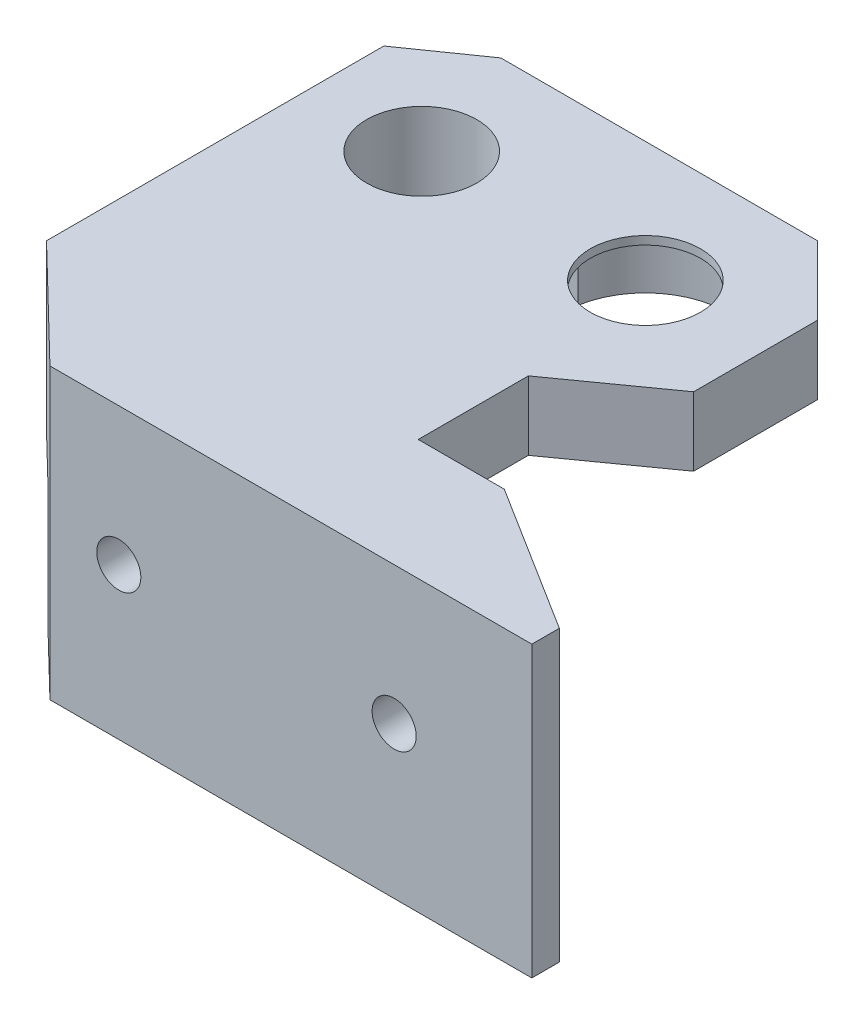
SolidWorks part; units mm, degrees
ref_plane "Front Plane" through (0, 0, 0) normal (0, 0, 1) x (1, 0, 0)
ref_plane "Top Plane" through (0, 0, 0) normal (0, 1, 0) x (1, 0, 0)
ref_plane "Right Plane" through (0, 0, 0) normal (1, 0, 0) x (0, 0, -1)
sketch "Sketch1" plane through (0, 0, 0) normal (0, 1, 0) x (1, 0, 0)
  line L0 (0, 0) -> (16.25, 0) construction
  line L5 (-3.75, 8.75) -> (19.25, 8.75)
  line L6 (19.25, 8.75) -> (24.25, 5.25)
  line L7 (24.25, 5.25) -> (24.25, -19.25)
  line L8 (24.25, -19.25) -> (16.25, -27)
  line L9 (16.25, -27) -> (-18.75, -27)
  line L10 (-18.75, -27) -> (-18.75, -25)
  line L11 (-18.75, -25) -> (-8, -18.25)
  line L12 (-8, -18.25) -> (-1.75, -18.25)
  line L13 (-1.75, -18.25) -> (-1.75, -10.25)
  line L14 (-1.75, -10.25) -> (-8.75, -5.25)
  line L15 (-8.75, -5.25) -> (-8.75, 3.75)
  line L16 (-8.75, 3.75) -> (-3.75, 8.75)
  line L17 (16.25, 0) -> (24.25, 0) construction
  circle A0 centre (0, 0) radius 4
  circle A1 centre (16.25, 0) radius 4
  point P0 (0, 0)
  dimension "D2" = 8
  dimension "D3" = 8
  dimension "D1" = 16.25
  dimension "D4" = 23
  dimension "D5" = 5
  dimension "D6" = 3.5
  dimension "D7" = 24.5
  dimension "D8" = 8
  dimension "D9" = 8.75
  dimension "D10" = 5
  dimension "D11" = 5
  dimension "D12" = 7
  dimension "D13" = 5
  dimension "D14" = 9
  dimension "D15" = 8
  dimension "D16" = 7.75
  dimension "D17" = 35
  dimension "D18" = 6.25
  dimension "D19" = 6.75
  dimension "D20" = 2
extrude "Boss-Extrude1" add sketch "Sketch1" along normal blind 5
sketch "Sketch2" plane through (0, 0, 0) normal (0, -1, 0) x (1, 0, 0)
  line L0 (24.25, 19.25) -> (24.25, -5.25)
  line L1 (24.25, -5.25) -> (20.75, -5.25)
  line L2 (20.75, -5.25) -> (20.75, 18.25)
  line L3 (20.75, 18.25) -> (-8, 18.25)
  line L4 (-8, 18.25) -> (-14.3704, 22.25)
  line L5 (-8, 18.25) -> (-18.75, 25) construction
  line L6 (-14.3704, 22.25) -> (21.1532, 22.25)
  line L7 (16.25, 27) -> (24.25, 19.25) construction
  line L8 (21.1532, 22.25) -> (24.25, 19.25)
  dimension "D1" = 3.5
  dimension "D2" = 4
extrude "Boss-Extrude2" add sketch "Sketch2" along normal blind 7
sketch "Sketch3" plane through (0, 0, 0) normal (0, -1, 0) x (1, 0, 0)
  line L5 (-14.3704, 22.25) -> (21.1532, 22.25)
  line L6 (21.1532, 22.25) -> (16.25, 27)
  line L7 (16.25, 27) -> (-18.75, 27)
  line L8 (-18.75, 27) -> (-18.75, 25)
  line L9 (-18.75, 25) -> (-14.3704, 22.25)
  line L10 (-14.3704, 22.25) -> (21.1532, 22.25)
  line L11 (21.1532, 22.25) -> (16.25, 27)
  line L12 (16.25, 27) -> (-18.75, 27)
  line L13 (-18.75, 27) -> (-18.75, 25)
  line L14 (-18.75, 25) -> (-14.3704, 22.25)
  dimension "D1" = 0
extrude "Boss-Extrude3" add sketch "Sketch3" along normal blind 16
sketch "Sketch6" plane through (0, 0, 0) normal (0, -1, 0) x (1, 0, 0)
  circle A0 centre (16.25, 0) radius 7
  circle A1 centre (16.25, 0) radius 4
  dimension "D1" = 14
extrude "Boss-Extrude4" add sketch "Sketch6" along normal blind 2.5
sketch "Sketch4" plane through (0, 0, 0) normal (0, -1, 0) x (1, 0, 0)
  line L0 (0, 0) -> (12.25, 0) construction
  line L1 (5.8838, -1) -> (12.377, -1)
  line L2 (5.8838, 1) -> (12.377, 1)
  line L3 (0, -1) -> (16.25, -1) construction
  line L4 (0, 1) -> (16.25, 1) construction
  line L5 (0, 0) -> (16.25, 0) construction
  arc A0 (5.8838, 1) -> (5.8838, -1) centre (0, 0) ccw
  arc A2 (12.377, 1) -> (12.377, -1) centre (16.25, 0) ccw
  dimension "D1" = 1
  dimension "D2" = 1
extrude "Cut-Extrude1" cut sketch "Sketch4" against normal blind 4.4
sketch "Sketch7" plane through (0, 4.4, 0) normal (0, -1, 0) x (1, 0, 0)
  line L2 (5.8838, -1) -> (12.377, -1)
  line L3 (12.377, 1) -> (5.8838, 1)
  line L4 (5.8838, -1) -> (12.377, -1)
  line L5 (12.377, 1) -> (5.8838, 1)
  arc A2 (5.8838, 1) -> (5.8838, -1) centre (0, 0) ccw
  arc A3 (12.377, 1) -> (12.377, -1) centre (16.25, 0) ccw
  arc A4 (5.8838, 1) -> (5.8838, -1) centre (0, 0) ccw
  arc A5 (12.377, 1) -> (12.377, -1) centre (16.25, 0) ccw
  dimension "D1" = 0
extrude "Cut-Extrude2" cut sketch "Sketch7" along normal through all
sketch "Sketch8" plane through (0, 0, 27) normal (0, 0, 1) x (1, 0, 0)
  line L0 (11.25, -5) -> (-8.75, -5) construction
  line L1 (-18.75, 5) -> (16.25, 5) construction
  line L2 (-18.75, 5) -> (-18.75, -16) construction
  circle A0 centre (11.25, -5) radius 1.6
  circle A1 centre (-8.75, -5) radius 1.6
  dimension "D1" = 3.2
  dimension "D2" = 3.2
  dimension "D3" = 20
  dimension "D4" = 10
  dimension "D5" = 10
extrude "Cut-Extrude3" cut sketch "Sketch8" against normal through all
sketch "Sketch9" plane through (0, 0, 18.25) normal (0, 0, -1) x (-1, 0, 0)
  circle A0 centre (-11.25, -5) radius 3
  circle A1 centre (8.75, -5) radius 3
  dimension "D1" = 6
  dimension "D2" = 6
extrude "Cut-Extrude4" cut sketch "Sketch9" against normal blind 4
mirror "Mirror1" about plane through (-18.75, 5, 27) normal (1, 0, 0) of "Boss-Extrude2", "Boss-Extrude4", "Cut-Extrude2", "Cut-Extrude3", "Cut-Extrude1", "Boss-Extrude3", "Boss-Extrude1", "Cut-Extrude4"
sketch "Sketch10" plane through (0, 5, 0) normal (0, 1, 0) x (1, 0, 0)
  line L0 (19.25, 8.75) -> (-3.75, 8.75) construction
  line L1 (30.4721, -27) -> (-18.75, -27)
  line L2 (30.4721, -27) -> (30.4721, 8.75)
  line L3 (30.4721, 8.75) -> (-18.75, 8.75)
  line L4 (-18.75, -27) -> (-18.75, 8.75)
  line L5 (30.4721, -27) -> (-18.75, 8.75) construction
  line L6 (30.4721, 8.75) -> (-18.75, -27) construction
  line L7 (16.25, -27) -> (-53.75, -27) construction
  point P0 (5.861, -9.125)
extrude "Cut-Extrude5" cut sketch "Sketch10" against normal through all
